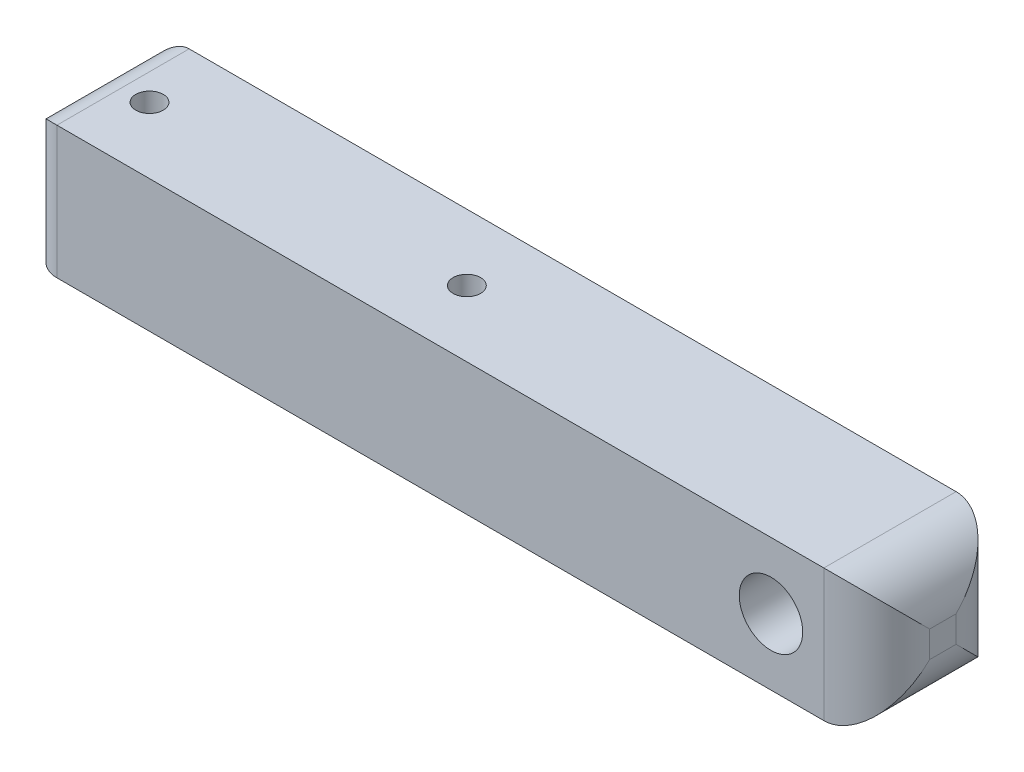
SolidWorks part; units mm, degrees
material "ABS"
ref_plane "Front Plane" through (0, 0, 0) normal (0, 0, 1) x (1, 0, 0)
ref_plane "Top Plane" through (0, 0, 0) normal (0, 1, 0) x (1, 0, 0)
ref_plane "Right Plane" through (0, 0, 0) normal (1, 0, 0) x (0, 0, -1)
sketch "Sketch1" plane through (0, 0, 0) normal (0, 0, 1) x (1, 0, 0)
  line L0 (0, 0) -> (101.6, 0)
  line L1 (101.6, 0) -> (101.6, 31.75)
  line L2 (101.6, 31.75) -> (-101.6, 31.75)
  line L3 (-101.6, 31.75) -> (-101.6, 0)
  line L4 (-101.6, 0) -> (0, 0)
  dimension "D1" = 31.75
  dimension "D2" = 203.2
extrude "Boss-Extrude1" add sketch "Sketch1" along normal mid plane 31.75
sketch "Sketch2" plane through (-101.6, 0, 0) normal (-1, 0, 0) x (0, 0, 1)
  line L0 (0, 5.4201) -> (-8.9803, 14.4003)
  line L1 (-8.9803, 14.4003) -> (-10.1028, 13.2778)
  line L2 (-10.1028, 13.2778) -> (0, 3.175)
  line L3 (0, 3.175) -> (10.1028, 13.2778)
  line L4 (10.1028, 13.2778) -> (8.9803, 14.4003)
  line L5 (8.9803, 14.4003) -> (0, 5.4201)
  line L6 (-11.3146, 0) -> (21.0706, 0) construction
  line L7 (-15.875, 31.75) -> (-15.875, 0) construction
  line L8 (-10.1028, 13.2778) -> (-15.875, 13.2778) construction
  line L9 (10.1028, 13.2778) -> (15.875, 13.2778) construction
  line L10 (15.875, 31.75) -> (15.875, 0) construction
  dimension "D1" = 1.5875
  dimension "D2" = 3.175
  dimension "D3" = 12.7
extrude "Cut-Extrude1" cut sketch "Sketch2" against normal blind 152.4
hole_wizard "1/2 (0.5) Diameter Hole1" positions "Sketch3" profile "Sketch4" hole size "1/2" standard "ANSI Inch" end condition through all
sketch "Sketch3" plane through (0, 0, 15.875) normal (0, 0, 1) x (1, 0, 0)
  line L0 (-101.6, 31.75) -> (-101.6, 0) construction
  line L1 (-101.6, 15.875) -> (162.3719, 15.875) construction
  point P0 (76.2, 15.875)
  dimension "D1" = 177.8
sketch "Sketch4" plane through (76.2, 15.875, 15.875) normal (1, 0, 0) x (0, -1, 0)
  line L0 (0, 0) -> (0, 31.75)
  line L1 (0, 31.75) -> (7.62, 31.75)
  line L2 (7.62, 31.75) -> (7.62, 0)
  line L5 (7.62, 0) -> (0, 0)
  line L11 (0, -6.35) -> (0, 107.95) construction
  dimension "Thru Hole Dia." = 15.24
  dimension "Thru Hole Depth" = 31.75
hole_wizard "1/4 (0.25) Diameter Hole1" positions "Sketch5" profile "Sketch6" hole size "1/4" standard "ANSI Inch" end condition through all
sketch "Sketch5" plane through (0, 31.75, 0) normal (0, 1, 0) x (1, 0, 0)
  line L0 (-101.6, -15.875) -> (-101.6, 15.875) construction
  point P0 (-88.9, 0)
  point P2 (-12.7, 0)
  dimension "D1" = 12.7
  dimension "D2" = 76.2
sketch "Sketch6" plane through (-88.9, 31.75, 0) normal (1, 0, 0) x (0, 0, 1)
  line L0 (0, 0) -> (0, 31.75)
  line L1 (0, 31.75) -> (3.302, 31.75)
  line L2 (3.302, 31.75) -> (3.302, 0)
  line L5 (3.302, 0) -> (0, 0)
  line L11 (0, -6.35) -> (0, 107.95) construction
  dimension "Thru Hole Dia." = 6.604
  dimension "Thru Hole Depth" = 31.75
fillet "Fillet1" radius 12.7 4 edges at (101.6, 0, 0) (101.6, 15.875, -15.875) (101.6, 31.75, 0) (101.6, 15.875, 15.875)
fillet "Fillet4" radius 6.35 3 edges at (-101.6, 15.875, 15.875) (-101.6, 31.75, 0) (-101.6, 15.875, -15.875)
